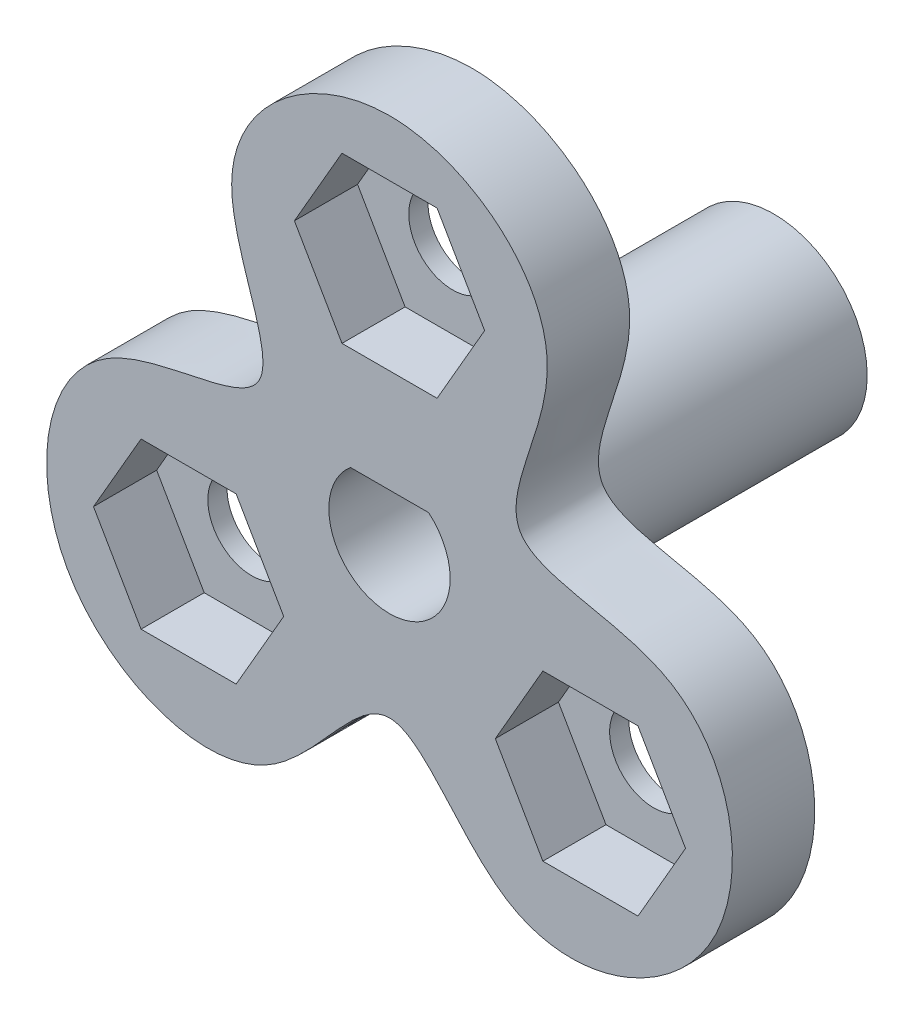
SolidWorks part; units mm, degrees
ref_plane "Front Plane" through (0, 0, 0) normal (0, 0, 1) x (1, 0, 0)
ref_plane "Top Plane" through (0, 0, 0) normal (0, 1, 0) x (1, 0, 0)
ref_plane "Right Plane" through (0, 0, 0) normal (1, 0, 0) x (0, 0, -1)
sketch "Sketch1" plane through (0, 0, 0) normal (0, 0, 1) x (1, 0, 0)
  line L0 (0, 2.21) -> (-0.9958, 2.21) construction
  line L1 (0, 2.21) -> (0.9958, 2.21) construction
  line L2 (-1.4241, 1.69) -> (1.4241, 1.69)
  line L3 (0, 0) -> (0, 13.5) construction
  line L4 (0, 13.5) -> (0, 8.45) construction
  line L5 (-3.4641, 8.45) -> (-5.7491, 8.45) construction
  line L6 (-3.4641, 8.45) -> (-1.7321, 5.45)
  line L7 (-1.7321, 5.45) -> (1.7321, 5.45)
  line L8 (1.7321, 5.45) -> (3.4641, 8.45)
  line L9 (3.4641, 8.45) -> (1.7321, 11.45)
  line L10 (1.7321, 11.45) -> (-1.7321, 11.45)
  line L11 (-1.7321, 11.45) -> (-3.4641, 8.45)
  line L12 (3.4641, 8.45) -> (5.7491, 8.45) construction
  line L13 (0, 0) -> (-2.9445, 1.7) construction
  line L14 (-2.9445, 1.7) -> (-4.7631, 2.75) construction
  line L15 (9.05, -1.225) -> (5.5859, -1.225)
  line L16 (5.5859, -1.225) -> (3.8538, -4.225)
  line L17 (3.8538, -4.225) -> (5.5859, -7.225)
  line L18 (5.5859, -7.225) -> (9.05, -7.225)
  line L19 (9.05, -7.225) -> (10.782, -4.225)
  line L20 (10.782, -4.225) -> (9.05, -1.225)
  line L21 (2.9445, 1.7) -> (4.7631, 2.75) construction
  line L22 (9.05, -1.225) -> (10.1925, 0.7539) construction
  line L23 (0, 0) -> (11.6913, -6.75) construction
  line L24 (5.5859, -7.225) -> (4.4433, -9.2039) construction
  line L25 (-5.5859, -7.225) -> (-3.8538, -4.225)
  line L26 (-3.8538, -4.225) -> (-5.5859, -1.225)
  line L27 (-5.5859, -1.225) -> (-9.05, -1.225)
  line L28 (-9.05, -1.225) -> (-10.782, -4.225)
  line L29 (-10.782, -4.225) -> (-9.05, -7.225)
  line L30 (-9.05, -7.225) -> (-5.5859, -7.225)
  line L31 (0, -3.4) -> (0, -5.5) construction
  line L32 (-5.5859, -7.225) -> (-4.4433, -9.2039) construction
  line L33 (0, 0) -> (-11.6913, -6.75) construction
  line L34 (-9.05, -1.225) -> (-10.1925, 0.7539) construction
  line L35 (-3.4641, 8.45) -> (3.4641, 8.45) construction
  circle A0 centre (0, 0) radius 2.21 construction
  arc A1 (-1.4241, 1.69) -> (1.4241, 1.69) centre (0, 0) ccw
  circle A2 centre (0, 8.45) radius 3 construction
  circle A3 centre (0, 8.45) radius 1.6
  circle A4 centre (0, 0) radius 3.4
  circle A5 centre (7.3179, -4.225) radius 1.6
  circle A6 centre (-7.3179, -4.225) radius 1.6
  spline S0 degree 3 poles (7.9187, 9.5658) (0, 15.7405) (-7.9187, 9.5658) (-2.4737, 1.4282) (-12.2436, 2.0749) (-13.6317, -7.8703) (-4.3248, -11.6407) (0, -2.8564) (4.3248, -11.6407) (13.6317, -7.8703) (12.2436, 2.0749) (2.4737, 1.4282) (7.9187, 9.5658) (0, 15.7405) (-7.9187, 9.5658) knots -0.238418 -0.166667 -0.094915 0 0.094915 0.166667 0.238418 0.333333 0.428249 0.5 0.571751 0.666667 0.761582 0.833333 0.905085 1 1.094915 1.166667 1.238418 only from (0, 13.5) to (0, 13.5)
  dimension "D2" = 4.42
  dimension "D8" = 6
  dimension "Wheel_Axle_Dia" = 6.8
  dimension "D3" = 3.2
  dimension "D1" = 0.52
  dimension "D4" = 5.05
  dimension "D5" = 60
  dimension "D7" = 8.45
  dimension "D9" = 8.45
  dimension "D6" = 3
extrude "Boss-Extrude1" add sketch "Sketch1" along normal blind 3 contours S0 L11 L10 L9 L8 L7 L6 L20 L19 L18 L17 L16 L15 L30 L29 L28 L27 L26 L25 A4 region at (0, -5.1586, 0)
extrude "Boss-Extrude2" add sketch "Sketch1<3>" along normal blind 0.7 separate body contours L29 L30 L25 L26 L27 L28 A6 | L10 L11 L6 L7 L8 L9 A3 | L19 L20 L15 L16 L17 L18 A5 region at (-2.5187, 9.9042, 0) region at (9.8366, -2.7708, 0) region at (-7.3179, -7.1333, 0)
sketch "Sketch1<3>" plane through (0, 0, 0) normal (0, 0, 1) x (1, 0, 0) same geometry as "Sketch1"
extrude "Boss-Extrude3" add sketch "Sketch1<4>" along normal blind 3 and the other way blind 11 contours A4 A1 L2 region at (-3.3038, 0, 0)
sketch "Sketch1<4>" plane through (0, 0, 0) normal (0, 0, 1) x (1, 0, 0) same geometry as "Sketch1"
combine bodies "Combine1" operation type add bodies to combine 103 104 105 106
equation "\"M3 Nut Diameter\" = 5.50mm"
equation "\"Clearance Diameter 3D Printing\" = .20mm"
equation "\"D-Shaft\"= 4mm'D-Shaft diameter"
equation "\"Wheel Axle Diameter\"= 6.8mm'Axle to Connect to Wheel"
equation "\"Wheel Thickness\"= 10mm'Wheel Thickness"
equation "\"D8@Sketch1\"=\"M3 Nut Diameter\" + \"Clearance Diameter 3D Printing\" + .30mm"
equation "\"D4@Sketch1\" = ( \"M3 Nut Diameter\" + \"Clearance Diameter 3D Printing\" + 0.40mm ) / 2 + 2mm"
equation "\"D2@Sketch1\"=\"D-Shaft\" + .42mm"
equation "\"Wheel_Axle_Dia@Sketch1\"= \"Wheel Axle Diameter\""
equation "\"D9@Sketch1\" = ( \"Wheel Axle Diameter\" / 2 ) + ( ( \"M3 Nut Diameter\" + \"Clearance Diameter 3D Printing\" + .40mm ) / 2 ) + 2mm"
equation "\"D2@Boss-Extrude3\"= \"Wheel Thickness\" + 1mm"
equation "\"M3 Screw Diameter\"= 3.20mm'M3 Screw Diameter already with 3D printing Clearance"
equation "\"D3@Sketch1\"= \"M3 Screw Diameter\""
equation "\"Wheel Diameter\"= 60mm"
equation "\"Silicone Tire Width\"= 7mm"
